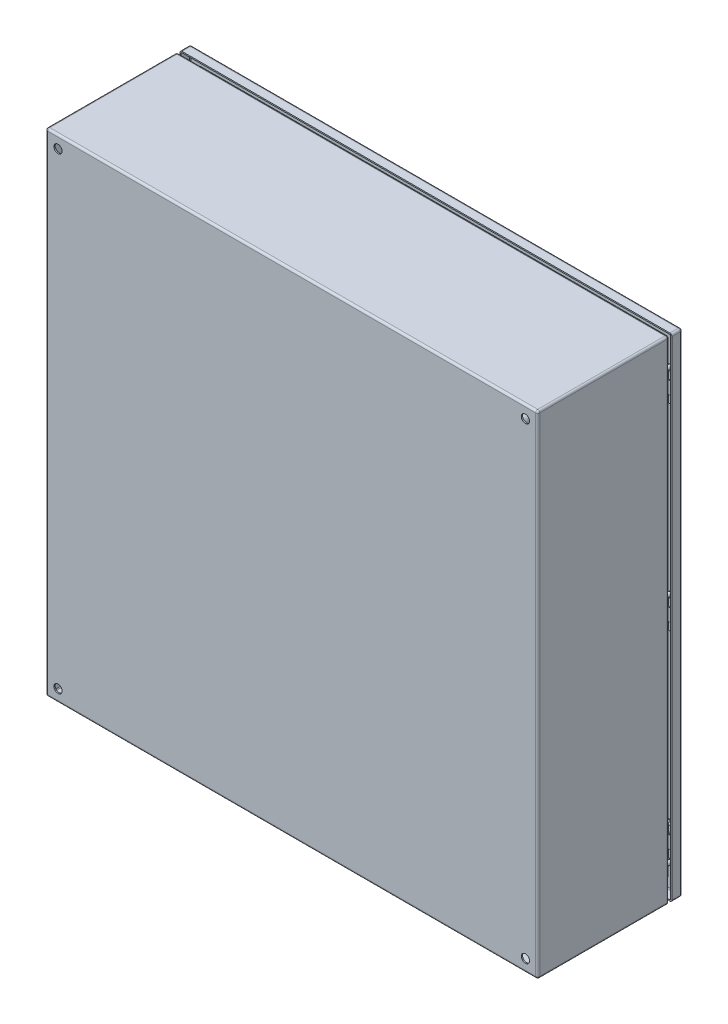
SolidWorks part; units mm, degrees
ref_plane "Front Plane" through (0, 0, 0) normal (0, 0, 1) x (1, 0, 0)
ref_plane "Top Plane" through (0, 0, 0) normal (0, 1, 0) x (1, 0, 0)
ref_plane "Right Plane" through (0, 0, 0) normal (1, 0, 0) x (0, 0, -1)
sketch "Sketch1" plane through (0, 0, 0) normal (0, 0, 1) x (1, 0, 0)
  line L0 (-381, -381) -> (381, 381) construction
  line L1 (-381, 381) -> (381, 381)
  line L2 (-381, 381) -> (-381, -381)
  line L3 (-381, -381) -> (381, -381)
  line L4 (381, 381) -> (381, -381)
  line L5 (-335.026, 381) -> (-335.026, -381) construction
  line L6 (-358.14, 358.14) -> (358.14, -358.14) construction
  line L7 (-358.14, 358.14) -> (358.14, 358.14)
  line L8 (-358.14, 358.14) -> (-358.14, -358.14)
  line L9 (-358.14, -358.14) -> (358.14, -358.14)
  line L10 (358.14, 358.14) -> (358.14, -358.14)
  line L11 (260.35, 0) -> (0, 0) construction
  line L16 (0, -361.95) -> (0, 361.95) construction
  line L21 (-361.95, 361.95) -> (361.95, 361.95) construction
  line L22 (-361.95, 361.95) -> (-361.95, -361.95) construction
  line L23 (-361.95, -361.95) -> (361.95, -361.95) construction
  line L24 (361.95, 361.95) -> (361.95, -361.95) construction
  line L25 (-361.95, 0) -> (361.95, 0) construction
  line L38 (-345.313, -345.313) -> (345.313, -345.313) construction
  line L39 (0, -345.313) -> (0, 0) construction
  line L40 (-345.313, -345.313) -> (-345.313, 345.313) construction
  line L41 (-345.313, 0) -> (0, 0) construction
  circle A16 centre (-345.313, 345.313) radius 3.9688
  circle A17 centre (345.313, 345.313) radius 3.9688
  circle A18 centre (-345.313, -345.313) radius 3.9688
  circle A19 centre (345.313, -345.313) radius 3.9688
  circle A20 centre (-361.95, 361.95) radius 6.35
  circle A21 centre (361.95, 361.95) radius 6.35
  circle A22 centre (361.95, -361.95) radius 6.35
  circle A23 centre (-361.95, -361.95) radius 6.35
  point P7 (-381, 0)
  point P8 (-381, 304.8)
  point P9 (-381, -304.8)
  dimension "D11" = 45.974
  dimension "D12" = 7.9375
  dimension "D4" = 12.7
  dimension "B" = 762
  dimension "D2" = 76.2
  dimension "A" = 762
  dimension "D3" = 76.2
  dimension "Panel Width" = 716.28
  dimension "Panel Height" = 716.28
  dimension "D6" = 690.626
  dimension "D7" = 690.626
  dimension "D8" = 19.05
  dimension "D9" = 19.05
sketch "Sketch2" plane through (0, 0, 0) normal (0, 1, 0) x (1, 0, 0)
  line L0 (0, 0) -> (0, 203.2) construction
  line L1 (0, 203.2) -> (0, 223.901) construction
  point P3 (0, 201.295)
  point P4 (0, 223.901)
  point P5 (0, 219.6148)
  point P7 (0, 214.2127)
  dimension "D1" = 22.606
  dimension "C" = 203.2
  dimension "wall thickness" = 1.905
  dimension "D3" = 4.2862
  dimension "D4" = 12.9177
sketch "Sketch3" plane through (0, 0, 0) normal (0, 0, 1) x (1, 0, 0)
  line L0 (-381, 381) -> (-381, -381) construction
  line L1 (-381, 381) -> (381, 381) construction
  line L2 (381, 381) -> (381, -381) construction
  line L3 (-381, -381) -> (381, -381) construction
  line L4 (-381, 381) -> (-381, -381)
  line L5 (-381, 381) -> (381, 381)
  line L6 (381, 381) -> (381, -381)
  line L7 (-381, -381) -> (381, -381)
extrude "Extrude1" add sketch "Sketch3" against normal up to vertex (203.2 mm away) up to point (0, 0, -203.2)
sketch "Sketch4" plane through (0, 0, -203.2) normal (0, 0, -1) x (-1, 0, 0)
  line L4 (362.077, 362.077) -> (-362.077, 362.077)
  line L5 (-362.077, 362.077) -> (-362.077, -362.077)
  line L6 (-362.077, -362.077) -> (362.077, -362.077)
  line L7 (362.077, -362.077) -> (362.077, 362.077)
  line L8 (360.172, 360.172) -> (-360.172, 360.172)
  line L9 (-360.172, 360.172) -> (-360.172, -360.172)
  line L10 (-360.172, -360.172) -> (360.172, -360.172)
  line L11 (360.172, -360.172) -> (360.172, 360.172)
  line L12 (360.172, 360.172) -> (-360.172, 360.172) construction
  line L13 (-360.172, 360.172) -> (-360.172, -360.172) construction
  line L14 (-360.172, -360.172) -> (360.172, -360.172) construction
  line L15 (360.172, -360.172) -> (360.172, 360.172) construction
  dimension "D1" = 20.828
  dimension "D2" = 1.905
extrude "Extrude2" add sketch "Sketch4" along normal up to vertex (11.0127 mm away) up to point (0, 0, -214.2127)
sketch "Sketch5" plane through (0, 0, -214.2127) normal (0, 0, -1) x (-1, 0, 0)
  line L4 (362.077, -362.077) -> (362.077, 362.077)
  line L5 (362.077, 362.077) -> (-362.077, 362.077)
  line L6 (-362.077, 362.077) -> (-362.077, -362.077)
  line L7 (-362.077, -362.077) -> (362.077, -362.077)
  line L8 (362.077, -362.077) -> (362.077, 362.077)
  line L9 (362.077, 362.077) -> (-362.077, 362.077)
  line L10 (-362.077, 362.077) -> (-362.077, -362.077)
  line L11 (-362.077, -362.077) -> (362.077, -362.077)
  dimension "D1" = 0
extrude "Extrude3" add sketch "Sketch5" along normal up to vertex (5.402 mm away) draft 13 up to point (0, 0, -219.6148) draft outward yes
fillet "Fillet1" radius 3.175 20 edges at (381, 0, 0) (0, -381, 0) (-381, 0, 0) (0, 381, 0) (362.077, -362.077, -208.7064) (362.7006, -362.7006, -216.9137) (-362.077, -362.077, -208.7064) (-362.7006, -362.7006, -216.9137) (362.7006, 362.7006, -216.9137) (362.077, 362.077, -208.7064) (-362.7006, 362.7006, -216.9137) (-362.077, 362.077, -208.7064) (0, -381, -203.2) (381, 0, -203.2) (0, 381, -203.2) (-381, 0, -203.2) (-381, 381, -101.6) (381, 381, -101.6) (-381, -381, -101.6) (381, -381, -101.6)
fillet "Fillet2" radius 1.5875 8 edges at (-361.1471, -361.1471, -203.2) (0, -362.077, -203.2) (361.1471, -361.1471, -203.2) (362.077, 0, -203.2) (361.1471, 361.1471, -203.2) (0, 362.077, -203.2) (-361.1471, 361.1471, -203.2) (-362.077, 0, -203.2)
shell "Shell1" thickness 1.905
sketch "Sketch6" plane through (0, 0, -1.905) normal (0, 0, -1) x (-1, 0, 0)
  circle A5 centre (361.95, -361.95) radius 6.35 construction
  circle A6 centre (-361.95, -361.95) radius 6.35 construction
  circle A7 centre (-361.95, 361.95) radius 6.35 construction
  circle A8 centre (361.95, 361.95) radius 6.35 construction
  circle A9 centre (361.95, -361.95) radius 6.35
  circle A12 centre (-361.95, -361.95) radius 6.35
  circle A13 centre (-361.95, 361.95) radius 6.35
  circle A18 centre (361.95, 361.95) radius 6.35
extrude "Cut-Extrude1" cut sketch "Sketch6" against normal through all
ref_plane "Plane1" through (0, 0, -23.876) normal (0, 0, 1) x (1, 0, 0)
sketch "Sketch8" plane through (0, 0, -1.905) normal (0, 0, -1) x (-1, 0, 0)
  circle A0 centre (-345.313, 345.313) radius 7.9375
  circle A1 centre (345.313, 345.313) radius 7.9375
  circle A2 centre (345.313, -345.313) radius 7.9375
  circle A3 centre (-345.313, -345.313) radius 7.9375
  circle A4 centre (-345.313, 345.313) radius 3.9688 construction
  circle A5 centre (345.313, 345.313) radius 3.9688 construction
  circle A6 centre (-345.313, 345.313) radius 3.9688
  circle A7 centre (345.313, 345.313) radius 3.9688
  circle A8 centre (345.313, -345.313) radius 3.9688 construction
  circle A9 centre (345.313, -345.313) radius 3.9688
  circle A10 centre (-345.313, -345.313) radius 3.9688 construction
  circle A11 centre (-345.313, -345.313) radius 3.9688
  dimension "D1" = 15.875
sketch "Sketch27" plane through (0, 0, -23.876) normal (0, 0, 1) x (1, 0, 0)
  line L0 (-358.14, -358.14) -> (358.14, -358.14) construction
  line L1 (358.14, 358.14) -> (358.14, -358.14) construction
  line L2 (-358.14, 358.14) -> (358.14, 358.14) construction
  line L3 (-358.14, 358.14) -> (-358.14, -358.14) construction
  line L4 (-358.14, -358.14) -> (358.14, -358.14)
  line L5 (358.14, 358.14) -> (358.14, -358.14)
  line L6 (-358.14, 358.14) -> (358.14, 358.14)
  line L7 (-358.14, 358.14) -> (-358.14, -358.14)
  circle A0 centre (-345.313, -345.313) radius 3.9688 construction
  circle A1 centre (345.313, -345.313) radius 3.9688 construction
  circle A2 centre (345.313, 345.313) radius 3.9688 construction
  circle A3 centre (-345.313, 345.313) radius 3.9688 construction
  circle A4 centre (-345.313, -345.313) radius 3.9688
  circle A5 centre (345.313, -345.313) radius 3.9688
  circle A6 centre (345.313, 345.313) radius 3.9688
  circle A7 centre (-345.313, 345.313) radius 3.9688
extrude "Extrude17" add sketch "Sketch27" against normal blind 1.524
extrude "Extrude5" add sketch "Sketch8" along normal up to surface (21.971 mm away) up to plane "Plane1"
ref_plane "Plane2" through (0, 0, -223.901) normal (0, 0, 1) x (1, 0, 0)
sketch "Sketch9" plane through (0, 0, -223.901) normal (0, 0, 1) x (1, 0, 0)
  line L0 (-381, -381) -> (381, -381) construction
  line L1 (381, 381) -> (381, -381) construction
  line L2 (-381, 381) -> (-381, -381) construction
  line L3 (-381, 381) -> (381, 381) construction
  line L4 (-381, -381) -> (381, -381)
  line L5 (381, 381) -> (381, -381)
  line L6 (-381, 381) -> (-381, -381)
  line L7 (-381, 381) -> (381, 381)
extrude "Extrude6" add sketch "Sketch9" along normal blind 16.002 separate body
fillet "Fillet3" radius 3.175 8 edges at (0, -381, -223.901) (381, 0, -223.901) (0, 381, -223.901) (-381, 0, -223.901) (381, -381, -215.9) (-381, -381, -215.9) (381, 381, -215.9) (-381, 381, -215.9)
shell "Shell2" thickness 1.905
ref_plane "Plane3" through (0, -304.8, 0) normal (0, 1, 0) x (-1, 0, 0)
sketch "Sketch13" plane through (0, -304.8, 0) normal (0, 1, 0) x (-1, 0, 0)
  line L0 (-374.142, -220.1418) -> (-366.9313, -220.1418)
  line L1 (-364.0582, -203.2) -> (-365.4044, -203.2)
  line L2 (-363.219, -217.1889) -> (-362.077, -212.2424)
  line L3 (-362.077, -212.2424) -> (-362.077, -205.1812)
  line L4 (-374.142, -218.694) -> (-366.9313, -218.694)
  line L5 (-364.6297, -216.8632) -> (-363.5248, -212.0774)
  line L6 (-363.5248, -212.0774) -> (-363.5248, -205.1812)
  line L7 (-364.0582, -204.6478) -> (-365.4044, -204.6478)
  line L8 (-365.4044, -203.2) -> (-365.4044, -204.6478)
  line L9 (-371.7394, -217.5372) -> (-370.6076, -218.44)
  line L10 (-377.825, -203.2) -> (377.825, -203.2) construction
  line L13 (-362.077, -204.7875) -> (-362.077, -214.2127) construction
  arc A0 (-370.6076, -218.44) -> (-374.142, -220.1418) centre (-374.142, -215.6206) ccw
  arc A1 (-366.9313, -220.1418) -> (-363.219, -217.1889) centre (-366.9313, -216.3318) ccw
  arc A2 (-362.077, -205.1812) -> (-364.0582, -203.2) centre (-364.0582, -205.1812) ccw
  arc A3 (-366.9313, -218.694) -> (-364.6297, -216.8632) centre (-366.9313, -216.3318) ccw
  arc A4 (-363.5248, -205.1812) -> (-364.0582, -204.6478) centre (-364.0582, -205.1812) ccw
  arc A5 (-371.7394, -217.5372) -> (-374.142, -218.694) centre (-374.142, -215.6206) ccw
  point P11 (-362.077, -203.2)
  dimension "D2" = 9.0424
  dimension "D4" = 3.81
  dimension "D7" = 1.9812
  dimension "D1" = 12.065
  dimension "D3" = 13
  dimension "D5" = 16.9418
  dimension "D6" = 3.3274
  dimension "D9" = 0.254
  dimension "D8" = 7.0612
  dimension "D10" = 1.4478
extrude "Extrude9" add sketch "Sketch13" along normal mid plane 43.9928 separate body
sketch "Sketch14" plane through (0, -304.8, 0) normal (0, 1, 0) x (-1, 0, 0)
  line L0 (-374.142, -220.1418) -> (-366.9313, -220.1418) construction
  line L1 (-378.6632, -220.1418) -> (-366.9313, -220.1418)
  line L2 (-378.6632, -220.1418) -> (-378.6632, -211.0994)
  line L3 (-378.6632, -211.0994) -> (-366.9313, -211.0994)
  line L4 (-366.9313, -220.1418) -> (-366.9313, -211.0994)
  arc A0 (-370.6076, -218.44) -> (-374.142, -220.1418) centre (-374.142, -215.6206) ccw construction
extrude "Cut-Extrude3" cut sketch "Sketch14" against normal mid plane 20.574
sketch "Sketch15" plane through (0, -294.513, 0) normal (0, -1, 0) x (1, 0, 0)
  circle A0 centre (374.142, -215.6206) radius 5.08
  circle A1 centre (374.142, -215.6206) radius 3.0734
  arc A2 (374.142, -218.694) -> (371.7394, -217.5372) centre (374.142, -215.6206) ccw construction
  dimension "D1" = 10.16
extrude "Extrude10" add sketch "Sketch15" along normal up to vertex (20.574 mm away) separate body up to point (366.9313, -315.087, -220.1418)
chamfer "Chamfer1" distance 0.508 angle 45 2 edges at (374.142, -294.513, -220.7006) (374.142, -315.087, -220.7006)
sketch "Sketch16" plane through (0, -326.7964, 0) normal (0, -1, 0) x (1, 0, 0)
  circle A0 centre (374.142, -215.6206) radius 3.0734
  arc A1 (374.142, -218.694) -> (371.7394, -217.5372) centre (374.142, -215.6206) ccw construction
extrude "Extrude11" add sketch "Sketch16" against normal up to vertex (43.9928 mm away) up to point (374.142, -282.8036, -220.1418)
sketch "Sketch17" plane through (0, -326.7964, 0) normal (0, -1, 0) x (1, 0, 0)
  circle A1 centre (374.142, -215.6206) radius 3.0734
  circle A2 centre (374.142, -215.6206) radius 3.0734
  dimension "D1" = 0
extrude "Extrude12" add sketch "Sketch17" along normal blind 1.524
sketch "Sketch18" plane through (0, -328.3204, 0) normal (0, -1, 0) x (1, 0, 0)
  line L0 (142.7154, -211.6582) -> (148.689, -211.6582) construction
  circle A1 centre (374.142, -215.6206) radius 3.0734
  circle A2 centre (374.142, -215.6206) radius 3.0734
  dimension "D2" = 3.9624
  dimension "D1" = 0
revolve "Revolve1" add sketch "Sketch18" angle 90 about L0
sketch "Sketch19" plane through (0, 0, -211.6582) normal (0, 0, 1) x (1, 0, 0)
  circle A1 centre (374.142, -332.2828) radius 3.0734
  circle A2 centre (374.142, -332.2828) radius 3.0734
  dimension "D1" = 0
extrude "Extrude13" add sketch "Sketch19" along normal blind 6.35
mirror "Mirror1" about plane through (0, 0, 0) normal (0, 1, 0) of bodies 117
pattern_linear "LPattern2" count 2 spacing 304.8 along (0, -1, 0) of bodies 123
sketch "Sketch21" plane through (0, 0, -223.901) normal (0, 0, -1) x (-1, 0, 0)
  line L0 (361.95, 0) -> (-361.95, 0) construction
  line L1 (335.026, 381) -> (335.026, -381) construction
  circle A0 centre (335.026, 0) radius 19.05
  dimension "D1" = 38.1
extrude "Extrude14" add sketch "Sketch21" along normal blind 2.286 separate body
sketch "Sketch22" plane through (0, 0, -226.187) normal (0, 0, -1) x (-1, 0, 0)
  circle A1 centre (335.026, 0) radius 19.05
  circle A2 centre (335.026, 0) radius 19.05
  dimension "D1" = 0
extrude "Extrude15" add sketch "Sketch22" along normal blind 3.175 draft 45
sketch "Sketch23" plane through (0, 0, -229.362) normal (0, 0, -1) x (-1, 0, 0)
  line L0 (335.026, 381) -> (335.026, -381) construction
  circle A0 centre (335.026, 0) radius 11.9063
  dimension "D1" = 23.8125
extrude "Cut-Extrude4" cut sketch "Sketch23" against normal blind 2.54
chamfer "Chamfer2" distance 0.381 angle 45 1 edges at (-346.9322, 0, -229.362)
sketch "Sketch24" plane through (0, 0, -226.822) normal (0, 0, -1) x (-1, 0, 0)
  line L0 (333.121, -6.8851) -> (333.121, -10.7156)
  line L1 (333.121, 10.7156) -> (336.931, 10.7156)
  line L2 (333.121, 10.7156) -> (333.121, 6.8851)
  line L3 (333.121, -10.7156) -> (336.931, -10.7156)
  line L4 (336.931, 10.7156) -> (336.931, 6.8851)
  line L5 (336.931, -6.8851) -> (336.931, -10.7156)
  line L6 (335.026, 0) -> (335.026, 10.7156) construction
  line L7 (335.026, 0) -> (335.026, -10.7156) construction
  circle A0 centre (335.026, 0) radius 12.2873 construction
  arc A1 (333.121, 6.8851) -> (333.121, -6.8851) centre (335.026, 0) ccw
  arc A3 (336.931, -6.8851) -> (336.931, 6.8851) centre (335.026, 0) ccw
  dimension "D1" = 14.2875
  dimension "D2" = 3.81
  dimension "D3" = 21.4312
extrude "Extrude16" add sketch "Sketch24" along normal blind 1.524
fillet "Fillet5" radius 0.381 12 edges at (-342.1697, 0, -228.346) (-335.026, 10.7156, -228.346) (-336.931, 8.8003, -228.346) (-336.931, -8.8003, -228.346) (-335.026, -10.7156, -228.346) (-333.121, -8.8003, -228.346) (-327.8822, 0, -228.346) (-333.121, 8.8003, -228.346) (-333.121, 10.7156, -227.584) (-333.121, -10.7156, -227.584) (-336.931, -10.7156, -227.584) (-336.931, 10.7156, -227.584)
sketch "Sketch25" plane through (0, 0, -228.346) normal (0, 0, -1) x (-1, 0, 0)
  circle A1 centre (335.026, 0) radius 2.7686
  dimension "D1" = 5.5372
extrude "Cut-Extrude5" cut sketch "Sketch25" against normal blind 1.27
sketch "Sketch26" plane through (0, 0, 0) normal (0, 1, 0) x (1, 0, 0)
  line L4 (-358.14, 23.876) -> (358.14, 23.876)
  line L5 (358.14, 23.876) -> (358.14, 25.4)
  line L6 (358.14, 25.4) -> (-358.14, 25.4)
  line L7 (-358.14, 25.4) -> (-358.14, 23.876)
  line L12 (-358.14, 23.876) -> (358.14, 23.876)
  line L13 (358.14, 23.876) -> (358.14, 25.4)
  line L14 (358.14, 25.4) -> (-358.14, 25.4)
  line L15 (-358.14, 25.4) -> (-358.14, 23.876)
  dimension "D1" = 0
pattern_linear "LPattern1" count 2 spacing 228.6 along (0, 1, 0) of bodies 122
mirror "Mirror2" about plane through (0, 0, 0) normal (0, 1, 0) of bodies 124
delete or keep bodies "Body-Delete1" type delete bodies bodies 122
sketch "Sketch28" plane through (0, 0, 0) normal (1, 0, 0) x (0, 0, -1)
  line L4 (23.876, 358.14) -> (23.876, -358.14)
  line L5 (25.4, 358.14) -> (23.876, 358.14)
  line L6 (25.4, -358.14) -> (25.4, 358.14)
  line L7 (23.876, -358.14) -> (25.4, -358.14)
  line L8 (23.876, 358.14) -> (23.876, -358.14)
  line L9 (25.4, 358.14) -> (23.876, 358.14)
  line L10 (25.4, -358.14) -> (25.4, 358.14)
  line L11 (23.876, -358.14) -> (25.4, -358.14)
  dimension "D1" = 0
sketch "Sketch29" plane through (0, 0, -223.901) normal (0, 0, -1) x (-1, 0, 0)
  line L0 (-377.825, 0) -> (377.825, 0) construction
  line L1 (-377.825, 377.825) -> (-377.825, -377.825) construction
  line L2 (377.825, -377.825) -> (377.825, 377.825) construction
  text T0 "RELAYS /\r\nPOWER \r\nSUPPLY" font "Arial" height in points 300
extrude "Cut-Extrude6" cut sketch "Sketch29" against normal blind 2.54
equation "\"D6@Sketch1\" = \"B@Sketch1\"-2.81"
equation "\"D7@Sketch1\" = \"A@Sketch1\"-2.81"
equation "\"D3@Sketch2\" = \"wall thickness@Sketch2\"*2.25"
equation "\"D4@Sketch2\" = \"D1@Sketch2\"/1.750"
equation "\"D2@Sketch4\" = \"wall thickness@Sketch2\""
equation "\"D1@Shell1\" = \"wall thickness@Sketch2\""
equation "\"D1@Fillet3\" = \"D1@Fillet1\""
equation "\"D1@Shell2\" = \"wall thickness@Sketch2\""
equation "\"D3@Sketch24\" = \"D1@Sketch24\"*1.5"
